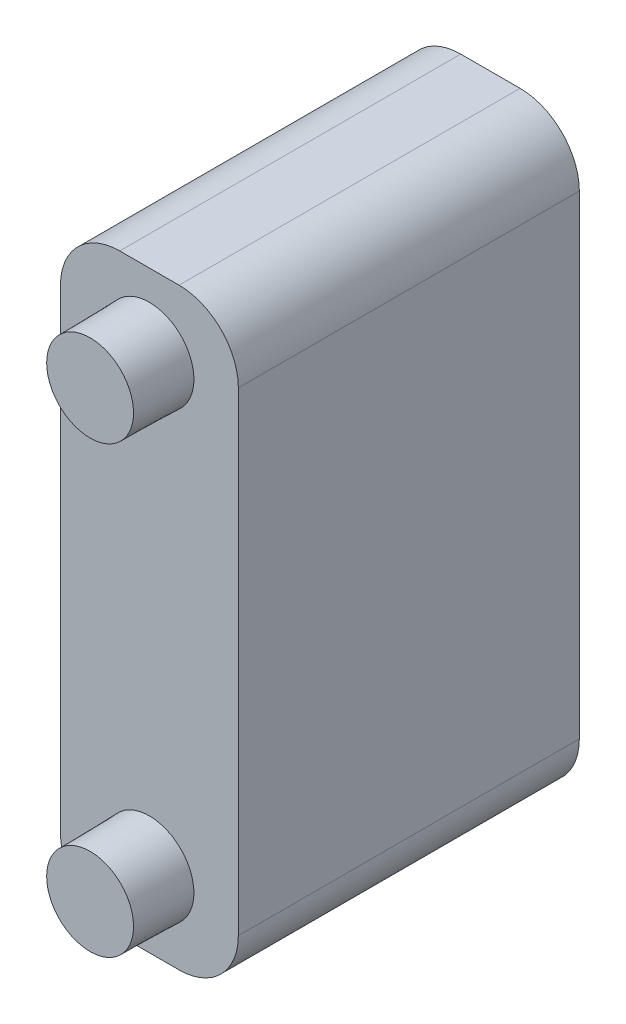
SolidWorks part; units mm, degrees
ref_plane "Front Plane" through (0, 0, 0) normal (1, 0, 0) x (0, 1, 0)
ref_plane "Top Plane" through (0, 0, 0) normal (0, 0, 1) x (0, 1, 0)
ref_plane "Right Plane" through (0, 0, 0) normal (0, 1, 0) x (-1, 0, 0)
sketch "Sketch1" plane through (0, 0, 0) normal (0, 0, 1) x (0, 1, 0)
  line L0 (4, 6) -> (4, 0) construction
  line L1 (2, 0) -> (18, 0)
  line L2 (0, 2) -> (0, 4)
  line L3 (2, 6) -> (18, 6)
  line L4 (20, 2) -> (20, 4)
  line L5 (16, 6) -> (16, 0) construction
  line L6 (10, 6) -> (10, 0) construction
  line L7 (0, 3) -> (20, 3) construction
  circle A0 centre (2.5, 3) radius 1.5
  circle A1 centre (17.5, 3) radius 1.5
  arc A2 (18, 6) -> (20, 4) centre (18, 4) cw
  arc A3 (18, 0) -> (20, 2) centre (18, 2) ccw
  arc A4 (2, 0) -> (0, 2) centre (2, 2) cw
  arc A5 (0, 4) -> (2, 6) centre (2, 4) cw
  point P13 (2.5, 3.2816)
  point P20 (20, 6)
  point P25 (0, 0)
  point P28 (0, 6)
  dimension "D2" = 3
  dimension "D5" = 2
  dimension "D1" = 20
  dimension "D3" = 12
  dimension "D4" = 6
extrude "Boss-Extrude1" add sketch "Sketch1" along normal blind 11.5 contours L1 A3 L4 A2 L3 A5 L2 A4
extrude "Boss-Extrude2" add sketch "Sketch1<3>" along normal blind 2 draft 1 from surface contours A0 | A1 starting at face at (-3, 10, 11.5)
sketch "Sketch1<3>" plane through (0, 0, 0) normal (0, 0, 1) x (0, 1, 0) same geometry as "Sketch1"
